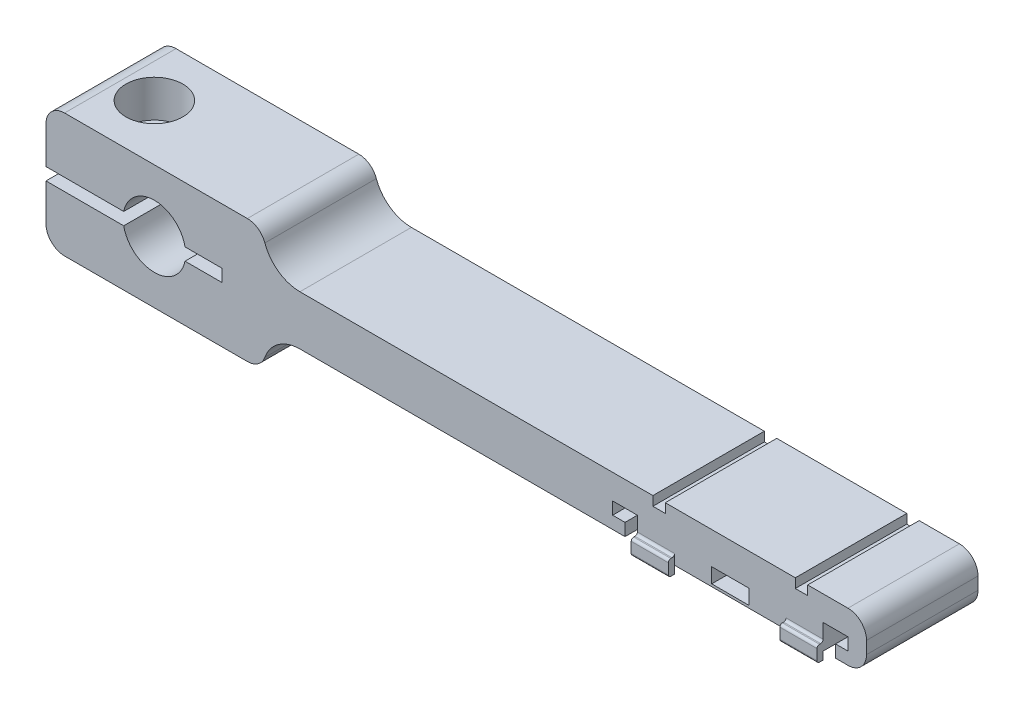
SolidWorks part; units mm, degrees
ref_plane "Front Plane" through (0, 0, 0) normal (0, 0, 1) x (1, 0, 0)
ref_plane "Top Plane" through (0, 0, 0) normal (0, 1, 0) x (1, 0, 0)
ref_plane "Right Plane" through (0, 0, 0) normal (1, 0, 0) x (0, 0, -1)
sketch "Sketch1" plane through (0, 0, 0) normal (0, 0, 1) x (1, 0, 0)
  line L2 (17.5, -4) -> (17.5, -10)
  line L3 (-17.5, 10) -> (17.5, 10)
  line L4 (-17.5, 10) -> (-17.5, 1)
  line L5 (-17.5, -10) -> (17.5, -10)
  line L6 (17.5, 10) -> (17.5, 4)
  line L7 (17.5, 4) -> (115, 4)
  line L9 (17.5, -4) -> (115, -4)
  line L10 (115, 4) -> (115, -4)
  line L11 (4.95, 0) -> (100, 0) construction
  line L12 (-17.5, -1) -> (-17.5, -10)
  line L13 (-17.5, -1) -> (-4.95, -1)
  line L15 (-17.5, 1) -> (-4.95, 1)
  line L17 (-17.5, -1) -> (-4.95, 1) construction
  line L18 (-17.5, 1) -> (-4.95, -1) construction
  line L20 (4.95, -1) -> (10.95, -1)
  line L22 (4.95, 1) -> (10.95, 1)
  line L23 (10.95, -1) -> (10.95, 1)
  line L24 (4.95, 0) -> (10.95, 1) construction
  line L25 (4.95, 0) -> (10.95, -1) construction
  arc A3 (-4.95, -1) -> (4.95, -1) centre (0, 0) ccw
  arc A4 (4.95, 1) -> (-4.95, 1) centre (0, 0) ccw
  point P1 (4.95, 0)
  point P5 (-11.225, 0)
  point P20 (0, -10)
  point P23 (115, 0)
  dimension "D1" = 10.1
  dimension "D2" = 2
  dimension "D3" = 20
  dimension "D4" = 15
  dimension "D5" = 8
  dimension "D6" = 35
  dimension "D7" = 100
  dimension "D8" = 6
extrude "beam footprint" add sketch "Sketch1" along normal blind 18
fillet "Fillet1" radius 6 2 edges at (17.5, -4, 9) (17.5, 4, 9)
fillet "Fillet2" radius 3 4 edges at (-17.5, 10, 9) (-17.5, -10, 9) (17.5, -10, 9) (17.5, 10, 9)
fillet "Fillet3" radius 3 2 edges at (115, -4, 9) (115, 4, 9)
sketch "Sketch7" plane through (0, 10, 0) normal (0, 1, 0) x (1, 0, 0)
  line L0 (-9, -9) -> (9, -9) construction
  line L2 (-14.5, 0) -> (-14.5, -18) construction
  circle A0 centre (-9, -9) radius 2.7
  circle A1 centre (9, -9) radius 2.7 construction
  point P7 (0, -9)
  point P9 (-14.5, -9)
  dimension "D2" = 5.4
  dimension "D1" = 18
extrude "M5 Bolt" cut sketch "Sketch7" against normal through all
ref_plane "Mid Beam plane" through (0, 0, 9) normal (0, 0, 1) x (1, 0, 0)
sketch "Sketch8" plane through (0, 0, 18) normal (0, 0, 1) x (1, 0, 0)
  line L0 (0, 0) -> (93, 0) construction
  line L1 (23.5, -4) -> (112, -4) construction
  line L2 (85.5, -4) -> (100.5, -4)
  line L3 (85.5, -4) -> (85.5, -1)
  line L4 (85.5, -1) -> (100.5, -1)
  line L5 (100.5, -4) -> (100.5, -1)
  line L6 (115, -1) -> (115, 1) construction
  point P9 (93, -1)
  point P12 (0, 0)
  dimension "D1" = 22
  dimension "D2" = 15
  dimension "D3" = 3
sketch "Sketch9" plane through (0, 0, 9) normal (0, 0, 1) x (1, 0, 0)
  line L4 (90, -4) -> (96, -4)
  line L5 (90, -4) -> (90, -1.2)
  line L6 (90, -1.2) -> (96, -1.2)
  line L7 (96, -4) -> (96, -1.2)
  line L8 (23.5, -4) -> (112, -4) construction
  line L9 (112, 4) -> (93, 4) construction
  line L10 (112, 4) -> (23.5, 4) construction
  point P9 (93, -1.2)
  dimension "D1" = 2.8
  dimension "D2" = 6
  dimension "D3" = 19
extrude "FS Cutout" cut sketch "Sketch9" against normal mid plane 12
sketch "Sketch10" plane through (0, 0, 9) normal (0, 0, 1) x (1, 0, 0)
  line L0 (112, 4) -> (23.5, 4) construction
  line L1 (80.5, 4) -> (82.5, 4)
  line L2 (80.5, 4) -> (80.5, 2.5)
  line L3 (80.5, 2.5) -> (82.5, 2.5)
  line L4 (82.5, 4) -> (82.5, 2.5)
  line L5 (82.5, 2.5) -> (103.5, 2.5) construction
  line L6 (103.5, 4) -> (105.5, 4)
  line L7 (103.5, 4) -> (103.5, 2.5)
  line L8 (103.5, 2.5) -> (105.5, 2.5)
  line L9 (105.5, 4) -> (105.5, 2.5)
  point P10 (93, 2.5)
  dimension "D1" = 2
  dimension "D2" = 1.5
  dimension "D3" = 25
sketch "Sketch16" plane through (0, -10, 0) normal (0, -1, 0) x (1, 0, 0)
  line L1 (-4.9, 9) -> (-6.95, 12.5507)
  line L2 (-6.95, 12.5507) -> (-11.05, 12.5507)
  line L3 (-11.05, 12.5507) -> (-13.1, 9)
  line L4 (-13.1, 9) -> (-11.05, 5.4493)
  line L5 (-11.05, 5.4493) -> (-6.95, 5.4493)
  line L6 (-6.95, 5.4493) -> (-4.9, 9)
  line L7 (0, 18) -> (0, 0) construction
  line L14 (0, 18) -> (93, 18) construction
  line L15 (-14.5, 18) -> (15.0147, 18) construction
  line L16 (6.95, 5.4493) -> (4.9, 9) construction
  line L17 (4.9, 9) -> (6.95, 12.5507) construction
  line L18 (11.05, 5.4493) -> (6.95, 5.4493) construction
  line L19 (13.1, 9) -> (11.05, 5.4493) construction
  line L20 (11.05, 12.5507) -> (13.1, 9) construction
  line L21 (6.95, 12.5507) -> (11.05, 12.5507) construction
  line L22 (9.35, 9) -> (-9.35, 9) construction
  circle A0 centre (-9, 9) radius 3.5507 construction
  circle A1 centre (9, 9) radius 3.5507 construction
  circle A5 centre (-9, 9) radius 2.7 construction
  dimension "D1" = 8.2
extrude "M5 Nut cutout" cut sketch "Sketch16" against normal blind 5
extrude "Rubber Band Notch" cut sketch "Sketch10" against normal through all both and the other way through all
sketch "Sketch13" plane through (0, 0, 3) normal (0, 0, 1) x (1, 0, 0)
  line L3 (96, -1.2) -> (90, -1.2) construction
  line L4 (96, -4) -> (96, -1.2) construction
  line L6 (90, -1.2) -> (96, -1.2)
  line L7 (90, -1.2) -> (90, -3.6)
  line L8 (90, -3.6) -> (96, -3.6)
  line L9 (96, -1.2) -> (96, -3.6)
  point P7 (96, -2.6)
  dimension "D1" = 2.4
extrude "Wire Cutout" cut sketch "Sketch13" against normal through all both and the other way through all
ref_plane "Mid FS plane" through (93, 0, 0) normal (1, 0, 0) x (0, 0, -1)
sketch "Sketch15" plane through (0, 10, 0) normal (0, 1, 0) x (1, 0, 0)
  circle A0 centre (-9, -9) radius 4.6
  circle A1 centre (7.5, -9) radius 4.6 construction
  dimension "D1" = 9.2
extrude "M5 Bolt Head" cut sketch "Sketch15" against normal blind 6
sketch "Sketch14" plane through (0, 0, 18) normal (0, 0, 1) x (1, 0, 0)
  line L0 (23.5, -4) -> (112, -4) construction
  line L1 (108, -4) -> (106, -4) construction
  line L4 (106, -4) -> (106, -2) construction
  line L5 (0, 0) -> (93, 0) construction
  line L6 (106, -2) -> (104, -2) construction
  line L7 (108, -4) -> (108, 0)
  line L8 (108, 0) -> (104, 0) construction
  line L9 (104, -2) -> (104, 0) construction
  line L10 (93, -4.18) -> (93, 4.18) construction
  line L18 (108, 0) -> (112, 0)
  line L19 (112, 0) -> (112, -2)
  line L20 (112, -2) -> (110, -2)
  line L21 (110, -2) -> (110, -4)
  line L22 (108, -4) -> (110, -4)
  line L23 (78, -4) -> (76, -4)
  line L24 (76, -2) -> (76, -4)
  line L25 (74, -2) -> (76, -2)
  line L26 (74, 0) -> (74, -2)
  line L27 (78, 0) -> (74, 0)
  line L28 (78, -4) -> (78, 0)
  point P2 (108, -2)
  dimension "D1" = 15
extrude "Slide Plate Cutout" cut sketch "Sketch14" against normal through all both
sketch "Sketch17" plane through (0, 0, 18) normal (0, 0, 1) x (1, 0, 0)
  line L0 (78, -4) -> (78, 0) construction
  line L1 (78, -5.25) -> (84, -5.25)
  line L2 (78, -5.25) -> (78, -2.75)
  line L3 (78, -2.75) -> (84, -2.75)
  line L4 (84, -5.25) -> (84, -2.75)
  line L5 (78, -4) -> (108, -4) construction
  line L6 (93, -4.18) -> (93, 4.18) construction
  line L7 (102, -5.25) -> (102, -2.75)
  line L8 (108, -2.75) -> (102, -2.75)
  line L9 (108, -5.25) -> (108, -2.75)
  line L10 (108, -5.25) -> (102, -5.25)
  point P9 (84, -4)
  dimension "D1" = 6
  dimension "D2" = 1.25
extrude "FS cover stop" add sketch "Sketch17" along normal blind 1
fillet "Fillet4" radius 0.4 6 edges at (81, -2.75, 19) (81, -2.75, 18) (81, -5.25, 19) (105, -2.75, 18) (105, -5.25, 19) (105, -2.75, 19)
